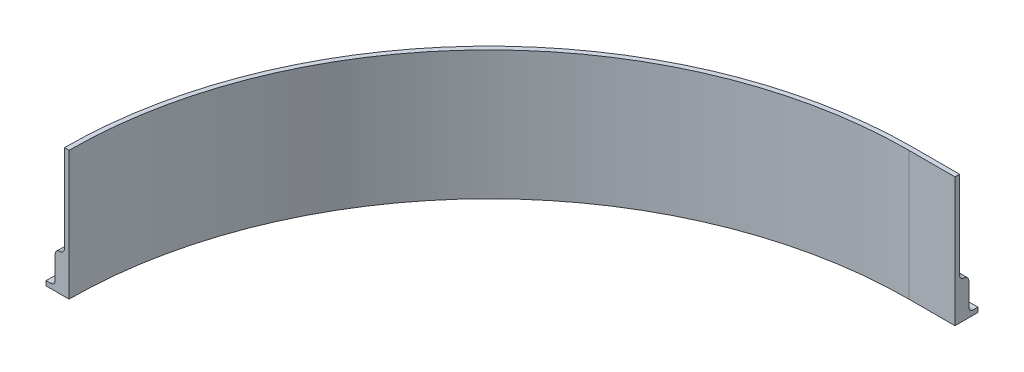
SolidWorks part; units mm, degrees
material "AISI 4340 Steel, annealed"
ref_plane "Front Plane" through (0, 0, 0) normal (0, 0, 1) x (1, 0, 0)
ref_plane "Top Plane" through (0, 0, 0) normal (0, 1, 0) x (1, 0, 0)
ref_plane "Right Plane" through (0, 0, 0) normal (1, 0, 0) x (0, 0, -1)
sketch "Sketch1" plane through (0, 0, 0) normal (0, 1, 0) x (1, 0, 0)
  line L0 (481, 481) -> (531, 481)
  line L1 (531, 481) -> (531, 456)
  line L2 (531, 456) -> (481, 456)
  line L3 (0, 0) -> (25, 0)
  arc A0 (0, 0) -> (481, 481) centre (481, 0) cw
  arc A1 (25, 0) -> (481, 456) centre (481, 0) cw
  point P3 (0, 0)
  dimension "D1" = 481
  dimension "D2" = 50
  dimension "D3" = 25
extrude "Bottom level" add sketch "Sketch1" along normal blind 5
sketch "Sketch2" plane through (0, 5, 0) normal (0, 1, 0) x (1, 0, 0)
  line L0 (481, 456) -> (531, 456) construction
  line L1 (481, 456) -> (531, 456)
  line L2 (481, 471) -> (531, 471)
  line L3 (531, 471) -> (531, 456)
  line L4 (10, 0) -> (25, 0)
  arc A0 (481, 456) -> (25, 0) centre (481, 0) ccw construction
  arc A1 (481, 456) -> (25, 0) centre (481, 0) ccw
  arc A2 (481, 471) -> (10, 0) centre (481, 0) ccw
  dimension "D1" = 15
extrude "Mid level" add sketch "Sketch2" along normal blind 35
sketch "Sketch3" plane through (0, 40, 0) normal (0, 1, 0) x (1, 0, 0)
  line L0 (481, 456) -> (531, 456) construction
  line L1 (481, 456) -> (531, 456)
  line L2 (481, 461) -> (531, 461)
  line L3 (531, 461) -> (531, 456)
  line L4 (20, 0) -> (25, 0)
  arc A0 (481, 456) -> (25, 0) centre (481, 0) ccw construction
  arc A1 (481, 456) -> (25, 0) centre (481, 0) ccw
  arc A2 (481, 461) -> (20, 0) centre (481, 0) ccw
  dimension "D1" = 5
extrude "Guard rail" add sketch "Sketch3" along normal blind 100
fillet "Rounding" radius 5 6 edges at (506, 40, -461) (506, 40, -471) (506, 5, -471) (155.0238, 40, -325.9762) (147.9527, 40, -333.0473) (147.9527, 5, -333.0473)
